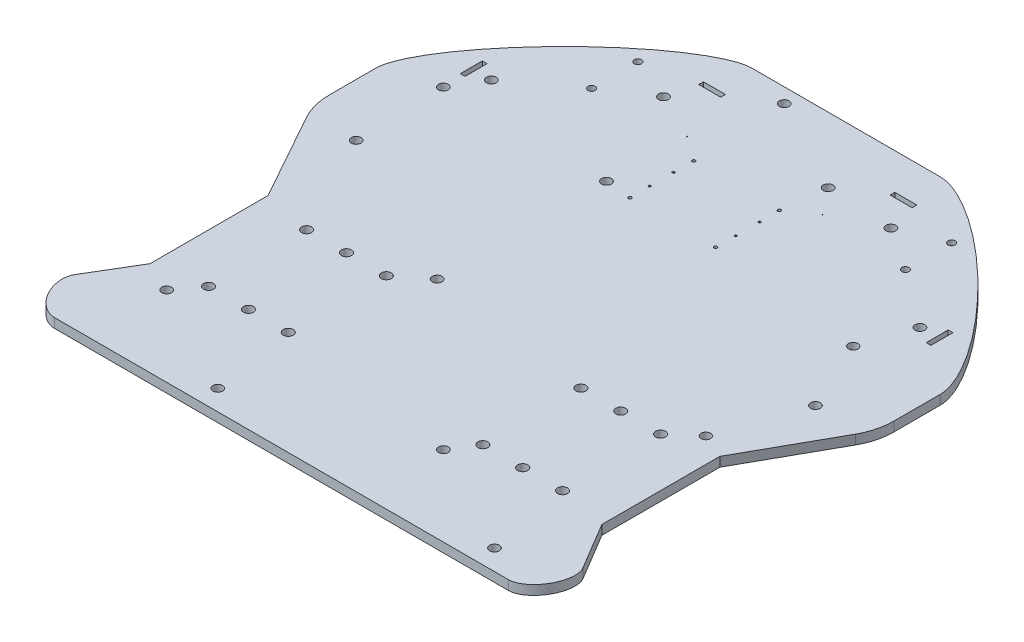
SolidWorks part; units mm, degrees
ref_plane "Front Plane" through (0, 0, 0) normal (0, 0, 1) x (1, 0, 0)
ref_plane "Top Plane" through (0, 0, 0) normal (0, 1, 0) x (1, 0, 0)
ref_plane "Right Plane" through (0, 0, 0) normal (1, 0, 0) x (0, 0, -1)
sketch "Sketch1" plane through (0, 0, 0) normal (0, 1, 0) x (1, 0, 0)
  line L0 (-90, 180) -> (-90, 0) construction
  line L1 (-180, 180) -> (0, 180)
  line L2 (-180, 180) -> (-180, 0)
  line L3 (-180, 0) -> (0, 0)
  line L4 (0, 180) -> (0, 0)
  line L5 (-180, 90) -> (0, 90) construction
  line L6 (-180, 30) -> (0, 30)
  line L7 (-130, 30) -> (-50, 30)
  line L8 (-130, 30) -> (-130, -30)
  line L9 (-130, -30) -> (-50, -30)
  line L10 (-50, 30) -> (-50, -30)
  line L11 (-130, 30) -> (-50, -30) construction
  line L12 (-130, -30) -> (-50, 30) construction
  dimension "D1" = 180
  dimension "D2" = 180
  dimension "D3" = 60
  dimension "D4" = 80
extrude "Boss-Extrude1" add sketch "Sketch1" along normal blind 3 contours L10 L3 L8 L9 | L2 L6 L4 L1 | L6 L10 L3 L4 | L8 L6 L2 L3 | L10 L6 L8 L3 region at (-90, 0, -105) region at (-155, 0, -15) region at (-25, 0, -15) region at (-90, 0, -15) region at (-90, 0, 15)
sketch "Sketch2" plane through (0, 3, 0) normal (0, 1, 0) x (1, 0, 0)
  line L0 (-180, 30) -> (0, 30)
  line L1 (-180, 180) -> (-180, 0) construction
  line L2 (0, 180) -> (0, 0) construction
  line L3 (-180, 180) -> (0, 180) construction
  line L4 (-90, 180) -> (-90, -30) construction
  line L5 (-130, -30) -> (-50, -30) construction
  dimension "D1" = 150
sketch "Sketch3" plane through (0, 3, 0) normal (0, 1, 0) x (1, 0, 0)
  line L0 (-180, 122) -> (0, 122)
  line L1 (-180, 180) -> (-180, 0) construction
  line L2 (0, 180) -> (0, 0) construction
  line L3 (-180, 30) -> (0, 30) construction
  dimension "D1" = 92
sketch "Sketch5" plane through (0, 3, 0) normal (0, 1, 0) x (1, 0, 0)
  line L0 (-114, 180) -> (-114, -30)
  line L1 (-180, 180) -> (0, 180) construction
  line L2 (-130, -30) -> (-50, -30) construction
  line L3 (-90, 180) -> (-90, -30) construction
  dimension "D1" = 24
fillet "Fillet1" radius 60 2 edges at (0, 1.5, -180) (-180, 1.5, -180) conic rho 0.2
sketch "Sketch6" plane through (0, 3, 0) normal (0, 1, 0) x (1, 0, 0)
  line L0 (-50, 0) -> (-130, 0)
  line L1 (-130, 0) -> (-130, -30)
  line L2 (-130, -30) -> (-50, -30)
  line L3 (-50, -30) -> (-50, 0)
  line L4 (-180, 0) -> (-162, 30.1113)
  line L5 (-162, 30.1113) -> (-162, 67.7113)
  line L6 (-162, 67.7113) -> (-180, 100)
  line L7 (-180, 120) -> (-180, 0) construction
  line L8 (-90, 180) -> (-90, -30) construction
  line L10 (-90, 180) -> (-90, 0) construction
  line L11 (0, 0) -> (-18, 30.1113)
  line L12 (-18, 30.1113) -> (-18, 67.7113)
  line L13 (-18, 67.7113) -> (0, 100)
  line M3 (0, 0) -> (0, 120)
  line M7 (-180, 120) -> (-180, 0)
  line M9 (-130, 0) -> (-130, -30)
  line M10 (-130, -30) -> (-50, -30)
  line M11 (-50, -30) -> (-50, 0)
  dimension "D1" = 37.6
  dimension "D2" = 72
  dimension "D3" = 100
extrude "Cut-Extrude1" cut sketch "Sketch6" against normal blind 10 contours L0 M11 M9 M10 | L5 L6 L4 M7 | L13 L12 L11 M3 region at (-90, 3, 15) region at (-172.3605, 3, -49.5379) region at (-7.6395, 3, -49.5379)
fillet "Fillet2" radius 10 2 edges at (-180, 1.5, 0) (0, 1.5, 0) conic rho 0.25
fillet "Fillet3" radius 20 2 edges at (-180, 1.5, -100) (0, 1.5, -100)
sketch "Sketch8" plane through (0, 3, 0) normal (0, 1, 0) x (1, 0, 0)
  line L1 (-63, 168.5) -> (-56, 168.5)
  line L2 (-63, 168.5) -> (-63, 167)
  line L3 (-63, 167) -> (-56, 167)
  line L4 (-56, 168.5) -> (-56, 167)
  line L5 (-117, 168.5) -> (-124, 168.5)
  line L6 (-117, 168.5) -> (-117, 167)
  line L7 (-117, 167) -> (-124, 167)
  line L8 (-124, 168.5) -> (-124, 167)
  line L9 (-165, 139) -> (-163.5, 139)
  line L10 (-165, 139) -> (-165, 132)
  line L11 (-165, 132) -> (-163.5, 132)
  line L12 (-163.5, 139) -> (-163.5, 132)
  line L13 (-16.5, 139) -> (-15, 139)
  line L14 (-16.5, 139) -> (-16.5, 132)
  line L15 (-16.5, 132) -> (-15, 132)
  line L16 (-15, 139) -> (-15, 132)
  circle A4 centre (-105.105, 175.3311) radius 1.55
  circle A5 centre (-74.9002, 159.1312) radius 1.55
  circle A8 centre (-112, 125.592) radius 1.55
  circle A9 centre (-164, 125.592) radius 1.55
  circle A10 centre (-112, 71.592) radius 1.55
  circle A11 centre (-146.4125, 64.417) radius 1.5875
  circle A12 centre (-133.7125, 64.417) radius 1.5875
  circle A13 centre (-121.0125, 64.417) radius 1.5875
  circle A14 centre (-146.4125, 33.175) radius 1.5875
  circle A15 centre (-133.7125, 33.175) radius 1.5875
  circle A16 centre (-121.0125, 33.175) radius 1.5875
  circle A17 centre (-58.9875, 64.417) radius 1.5875
  circle A18 centre (-46.2875, 64.417) radius 1.5875
  circle A19 centre (-33.5875, 64.417) radius 1.5875
  circle A20 centre (-33.5875, 33.175) radius 1.5875
  circle A21 centre (-46.2875, 33.175) radius 1.5875
  circle A22 centre (-58.9875, 33.175) radius 1.5875
  circle A23 centre (-63.9, 25.5) radius 1.55
  circle A24 centre (-28.6, 6.5) radius 1.55
  circle A25 centre (-116.8, 6.5) radius 1.55
  circle A26 centre (-152.1, 25.5) radius 1.55
  circle A27 centre (-27.14, 119.392) radius 1.5
  circle A28 centre (-25.87, 71.132) radius 1.5
  dimension "D3" = 3.1
  dimension "D4" = 3.1
  dimension "D5" = 3.1
  dimension "D6" = 3.1
  dimension "D7" = 3.1
  dimension "D8" = 3.175
  dimension "D9" = 3.175
  dimension "D10" = 3.175
  dimension "D11" = 3.175
  dimension "D12" = 3.175
  dimension "D13" = 3.175
  dimension "D14" = 3.1
  dimension "D15" = 3.1
  dimension "D16" = 3.1
  dimension "D17" = 3.1
  dimension "D18" = 3.175
  dimension "D19" = 3.175
  dimension "D20" = 3.175
  dimension "D21" = 3.175
  dimension "D22" = 3.175
  dimension "D23" = 3.175
  dimension "D24" = 3
  dimension "D25" = 3
extrude "Cut-Extrude2" cut sketch "Sketch8" against normal up to next (3 mm away)
sketch "Sketch9" plane through (0, 0, 0) normal (0, -1, 0) x (1, 0, 0)
  line L1 (-68.18, -150.89) -> (-68.42, -150.89)
  line L2 (-68.18, -150.89) -> (-68.18, -150.65)
  line L3 (-68.18, -150.65) -> (-68.42, -150.65)
  line L4 (-68.42, -150.89) -> (-68.42, -150.65)
  line L5 (-111.36, -150.89) -> (-111.6, -150.89)
  line L6 (-111.36, -150.89) -> (-111.36, -150.65)
  line L7 (-111.36, -150.65) -> (-111.6, -150.65)
  line L8 (-111.6, -150.89) -> (-111.6, -150.65)
  line L9 (-76.01, -139.0625) -> (-76.645, -139.0625)
  line L10 (-76.01, -139.0625) -> (-76.01, -138.4275)
  line L11 (-76.01, -138.4275) -> (-76.645, -138.4275)
  line L12 (-76.645, -139.0625) -> (-76.645, -138.4275)
  line L13 (-76.01, -131.4425) -> (-76.645, -131.4425)
  line L14 (-76.01, -131.4425) -> (-76.01, -130.8075)
  line L15 (-76.01, -130.8075) -> (-76.645, -130.8075)
  line L16 (-76.645, -131.4425) -> (-76.645, -130.8075)
  line L17 (-103.47, -139.0625) -> (-104.105, -139.0625)
  line L18 (-103.47, -139.0625) -> (-103.47, -138.4275)
  line L19 (-103.47, -138.4275) -> (-104.105, -138.4275)
  line L20 (-104.105, -139.0625) -> (-104.105, -138.4275)
  line L21 (-103.47, -131.4425) -> (-104.105, -131.4425)
  line L22 (-103.47, -131.4425) -> (-103.47, -130.8075)
  line L23 (-103.47, -130.8075) -> (-104.105, -130.8075)
  line L24 (-104.105, -131.4425) -> (-104.105, -130.8075)
  circle A0 centre (-163.2, -97) radius 1.55
  circle A1 centre (-158.3, -135.2) radius 1.55
  circle A2 centre (-126.25, -158) radius 1.55
  circle A3 centre (-53.75, -158) radius 1.55
  circle A4 centre (-21.7, -135.2) radius 1.55
  circle A5 centre (-16.8, -97) radius 1.55
  circle A6 centre (-76.405, -124.775) radius 0.5
  circle A7 centre (-103.71, -145.095) radius 0.5
  circle A8 centre (-76.405, -145.095) radius 0.5
  circle A9 centre (-103.71, -124.775) radius 0.5
  circle A10 centre (-140, -148.857) radius 1.143
  circle A11 centre (-140, -163.589) radius 1.143
  circle A12 centre (-40, -148.857) radius 1.143
  circle A13 centre (-40, -163.589) radius 1.143
  dimension "D1" = 3.1
  dimension "D2" = 3.1
  dimension "D3" = 3.1
  dimension "D4" = 3.1
  dimension "D5" = 3.1
  dimension "D6" = 3.1
  dimension "D7" = 1
  dimension "D8" = 1
  dimension "D9" = 1
  dimension "D10" = 1
  dimension "D11" = 2.286
  dimension "D12" = 2.286
  dimension "D13" = 2.286
  dimension "D14" = 2.286
extrude "Cut-Extrude3" cut sketch "Sketch9" against normal up to next
